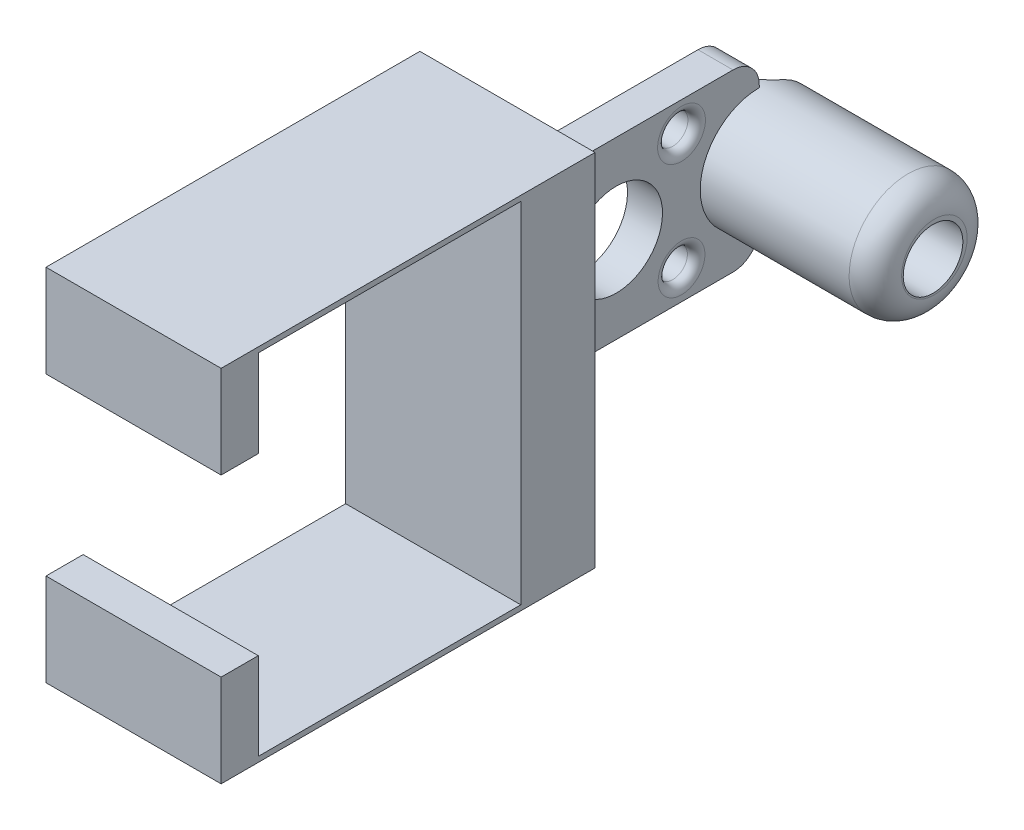
SolidWorks part; units mm, degrees
ref_plane "Front Plane" through (0, 0, 0) normal (1, 0, 0) x (0, 1, 0)
ref_plane "Top Plane" through (0, 0, 0) normal (0, 0, 1) x (0, 1, 0)
ref_plane "Right Plane" through (0, 0, 0) normal (0, 1, 0) x (-1, 0, 0)
sketch "Sketch1" plane through (0, 0, 0) normal (1, 0, 0) x (0, 1, 0)
  line L3 (11.3363, 55.2987) -> (24.7475, 55.2987)
  line L4 (24.7475, 55.2987) -> (24.7475, 49.9139)
  line L10 (63.5333, 55.2987) -> (63.5333, 1.0697)
  line L11 (63.5333, 1.0697) -> (11.3363, 1.0697)
  line L12 (24.7475, 49.9139) -> (12.0983, 49.9139)
  line L13 (12.0983, 49.9139) -> (12.0983, 11.8393)
  line L14 (12.0983, 11.8393) -> (62.7713, 11.8393)
  line L15 (63.5333, 55.2987) -> (50.1221, 55.2987)
  line L16 (50.1221, 55.2987) -> (50.1221, 49.9139)
  line L17 (50.1221, 49.9139) -> (62.7713, 49.9139)
  line L18 (62.7713, 49.9139) -> (62.7713, 11.8393)
  line L20 (11.3363, 55.2987) -> (11.3363, 1.0697)
  dimension "D1" = 50.673
  dimension "D2" = 12.6492
  dimension "D3" = 12.6492
  dimension "D4" = 5.3848
  dimension "D5" = 5.3848
  dimension "D6" = 10.7696
  dimension "D7" = 0.762
  dimension "D8" = 0.762
  dimension "D9" = 38.0746
  dimension "D10" = 38.0746
extrude "Boss-Extrude1" add sketch "Sketch1" along normal blind 25.4
sketch "Sketch3" plane through (0, 0, 1.0697) normal (0, 0, -1) x (1, 0, 0)
  line L1 (11.1207, -49.6132) -> (6.0407, -49.6132)
  line L2 (11.1207, -49.6132) -> (11.1207, -24.2132)
  line L3 (11.1207, -24.2132) -> (6.0407, -24.2132)
  line L4 (6.0407, -49.6132) -> (6.0407, -24.2132)
  point P0 (12.7, -37.4348)
  dimension "D1" = 5.08
  dimension "D2" = 25.4
extrude "Boss-Extrude2" add sketch "Sketch3" along normal blind 38.1
sketch "Sketch5" plane through (11.1207, 0, 0) normal (1, 0, 0) x (0, 1, 0)
  line L0 (49.6132, -37.0303) -> (24.2132, -37.0303) construction
  circle A0 centre (36.9132, -37.0303) radius 8.5598
  dimension "D1" = 17.1196
extrude "Boss-Extrude3" add sketch "Sketch5" along normal blind 25.4
sketch "Sketch6" plane through (11.1207, 0, 0) normal (1, 0, 0) x (0, 1, 0)
  circle A0 centre (36.76, -16.2764) radius 6.7201
extrude "Cut-Extrude1" cut sketch "Sketch6" against normal through all
fillet "Fillet1" radius 3.81 1 edges at (11.1207, 36.9132, -37.0303)
fillet "Fillet2" radius 3.81 4 edges at (8.5807, 49.6132, 1.0697) (8.5807, 24.2132, 1.0697) (11.1207, 36.9132, 1.0697) (6.0407, 36.9132, 1.0697)
sketch "Sketch7" plane through (36.5207, 0, 0) normal (1, 0, 0) x (0, 1, 0)
  circle A0 centre (36.7784, -36.8329) radius 4.3245
extrude "Cut-Extrude2" cut sketch "Sketch7" against normal mid plane 25.4
fillet "Fillet3" radius 3.81 1 edges at (23.8207, 41.103, -36.8329)
sketch "Sketch8" plane through (11.1207, 0, 0) normal (1, 0, 0) x (0, 1, 0)
  circle A0 centre (28.4911, -25.7552) radius 2.1224
  circle A1 centre (45.3217, -25.7552) radius 2.1973
  circle A2 centre (45.3217, -6.4) radius 2.3381
  circle A3 centre (28.4911, -6.4) radius 2.0571
extrude "Cut-Extrude3" cut sketch "Sketch8" against normal through all
fillet "Fillet4" radius 3.81 3 edges at (36.5207, 45.473, -37.0303) (8.5807, 49.6132, -37.0303) (8.5807, 24.2132, -37.0303)
fillet "Fillet5" radius 1.27 8 edges at (6.0407, 30.6135, -25.7552) (6.0407, 47.519, -25.7552) (6.0407, 47.6597, -6.4) (6.0407, 30.5482, -6.4) (11.1207, 47.519, -25.7552) (11.1207, 30.6135, -25.7552) (11.1207, 30.5482, -6.4) (11.1207, 47.6597, -6.4)
equation "\"F_Load\"= 600"
equation "\"SF\"= 4"
equation "\"S_y\"= 40000"
equation "\"E_mod\"= 10000000"
equation "\"S_allow\"= \"S_y\" / \"SF\""
equation "\"Bracket_depth\"= 1in"
equation "\"Pin_Radius\"= ( ( 2 * \"F_Load\" * 1.0 ) / ( PI * \"S_allow\" ) ) ^ ( 1 / 3 )"
equation "\"Pin_Diameter\"= 2 * \"Pin_Radius\""
equation "\"Arm_thickness\"= \"F_Load\" / ( \"Bracket_depth\" * \"S_allow\" )"
equation "\"Arm_Height\"= 1.5in"
equation "\"Base_Thickness\"= sqr ( ( ( 1.5 * \"F_Load\" * 2.0 ) / ( \"Bracket_depth\" * \"S_allow\" ) ) )"
equation "\"Base_Span\"= 1.995in"
equation "\"Wall_Thickness\"= ( \"F_Load\" / 2 ) / ( \"Bracket_depth\" * \"S_allow\" )"
equation "\"Wall_height\"= 1.499in"
equation "\"Flange_thickness\"= sqr ( ( ( 1.5 * \"F_Load\" * 0.498 ) / ( \"Bracket_depth\" * \"S_allow\" ) ) )"
equation "\"Flange_Overhang\"= 0.498in"
equation "\"Fit_b_Opening\"= 0.9992in"
